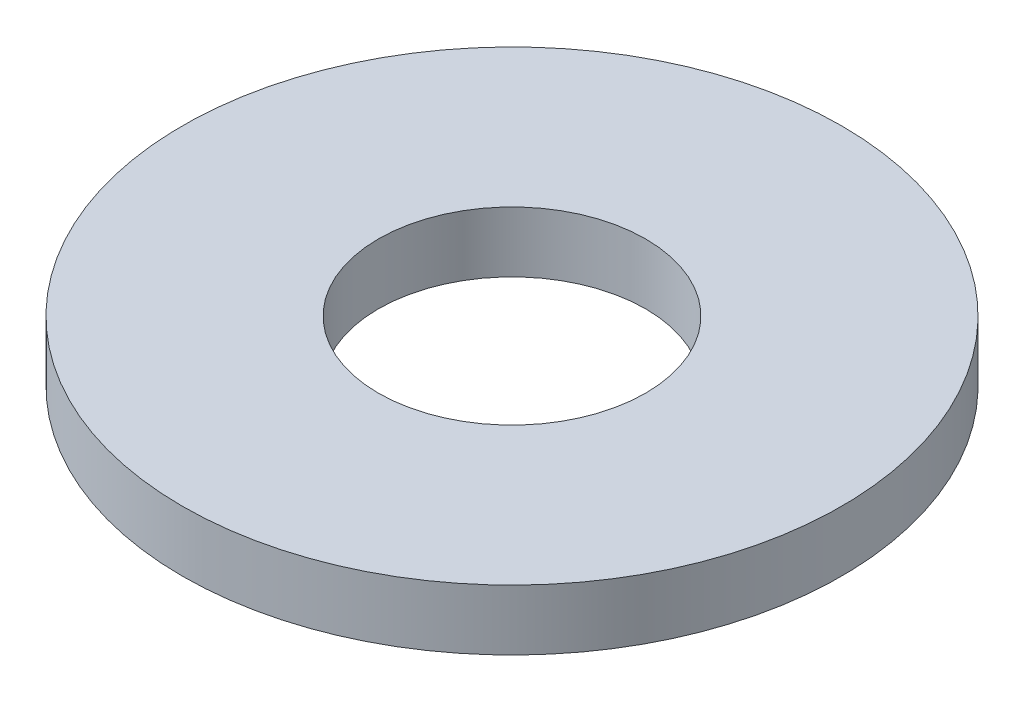
SolidWorks part; units mm, degrees
ref_plane "Front Plane" through (0, 0, 0) normal (0, 0, 1) x (1, 0, 0)
ref_plane "Top Plane" through (0, 0, 0) normal (0, 1, 0) x (1, 0, 0)
ref_plane "Right Plane" through (0, 0, 0) normal (1, 0, 0) x (0, 0, -1)
sketch "Sketch1" plane through (0, 0, 0) normal (0, 1, 0) x (1, 0, 0)
  circle A0 centre (0, 0) radius 92.5
  dimension "FLANGE_OD" = 185
extrude "Boss-Extrude1" add sketch "Sketch1" along normal blind 17
sketch "Sketch2" plane through (0, 0, 0) normal (0, 1, 0) x (1, 0, 0)
  circle A0 centre (0, 0) radius 37.5
  dimension "BORE_D" = 75
extrude "Cut-Extrude1" cut sketch "Sketch2" along normal through all
sketch "Sketch3" plane through (0, 17, 0) normal (0, 1, 0) x (1, 0, 0)
  circle A0 centre (0, 0) radius 28.4738 construction
  circle A1 centre (-28.4738, 0) radius 4.2448
  dimension "BOLT_D" = 8.4896
  dimension "BOLT_PCD" = 56.9476
extrude "Cut-Extrude2" cut sketch "Sketch3" against normal blind 10.8537 rebuild error yes
pattern_circular "CirPattern1" count 5 over 360 rebuild error yes
